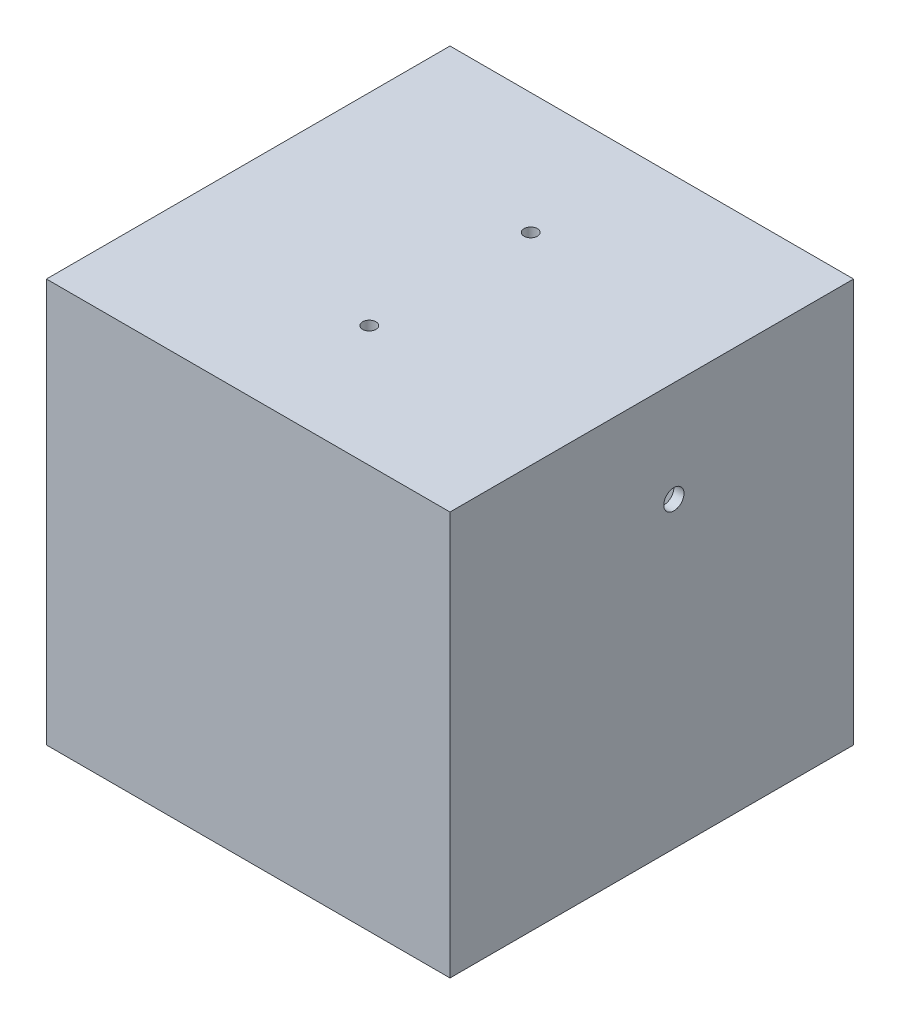
SolidWorks part; units mm, degrees
ref_plane "前视基准面" through (0, 0, 0) normal (0, 0, 1) x (1, 0, 0)
ref_plane "上视基准面" through (0, 0, 0) normal (0, 1, 0) x (1, 0, 0)
ref_plane "右视基准面" through (0, 0, 0) normal (1, 0, 0) x (0, 0, -1)
sketch "草图1" plane through (0, 0, 0) normal (0, 1, 0) x (1, 0, 0)
  line L1 (0, 0) -> (200, 0)
  line L2 (0, 0) -> (0, 200)
  line L3 (0, 200) -> (200, 200)
  line L4 (200, 0) -> (200, 200)
  dimension "D1" = 200
  dimension "D2" = 200
extrude "凸台-拉伸1" add sketch "草图1" along normal blind 5
sketch "草图3" plane through (0, 0, 0) normal (0, -1, 0) x (1, 0, 0)
  line L0 (0, -100) -> (200, -100) construction
  line L1 (0, -200) -> (0, 0) construction
  line L2 (200, 0) -> (200, -200) construction
  line L3 (0, 0) -> (200, 0) construction
  line L4 (0, -200) -> (200, -200)
  line L5 (0, -200) -> (0, 0)
  line L6 (0, 0) -> (200, 0)
  line L7 (200, -200) -> (200, 0)
  line L8 (0, -200) -> (200, 0) construction
  line L9 (0, 0) -> (200, -200) construction
  line L11 (5, -5) -> (195, -5)
  line L12 (5, -5) -> (5, -195)
  line L13 (5, -195) -> (195, -195)
  line L14 (195, -5) -> (195, -195)
  line L15 (5, -5) -> (195, -195) construction
  line L16 (5, -195) -> (195, -5) construction
  point P6 (100, -100)
  point P13 (100, -100)
  dimension "D1" = 190
extrude "凸台-拉伸2" add sketch "草图3" along normal blind 190
sketch "草图4" plane through (0, -190, 0) normal (0, -1, 0) x (1, 0, 0)
  line L0 (100, 0) -> (100, -200) construction
  line L1 (0, 0) -> (200, 0)
  line L2 (0, 0) -> (0, -200)
  line L3 (0, -200) -> (200, -200)
  line L4 (200, 0) -> (200, -200)
  circle A0 centre (100, -100) radius 70
  dimension "D1" = 140
extrude "凸台-拉伸3" add sketch "草图4" along normal blind 5
sketch "草图5" plane through (0, 5, 0) normal (0, 1, 0) x (1, 0, 0)
  line L0 (0, 100) -> (200, 100) construction
  line L1 (0, 200) -> (0, 0) construction
  line L2 (200, 0) -> (200, 200) construction
  line L3 (100, 100) -> (100, 200) construction
  line L4 (200, 200) -> (0, 200) construction
  circle A0 centre (100, 140) radius 3.3
  circle A1 centre (100, 60) radius 3.3
  dimension "D1" = 6.6
  dimension "D2" = 40
extrude "切除-拉伸1" cut sketch "草图5" against normal blind 5
sketch "草图7" plane through (200, 0, 0) normal (1, 0, 0) x (0, 0, -1)
  line L0 (200, 5) -> (200, -195) construction
  line L4 (0, 5) -> (200, 5) construction
  circle A0 centre (110.95, -45) radius 5
  dimension "D2" = 10
  dimension "D1" = 89.05
  dimension "D3" = 50
extrude "切除-拉伸2" cut sketch "草图7" against normal through all
